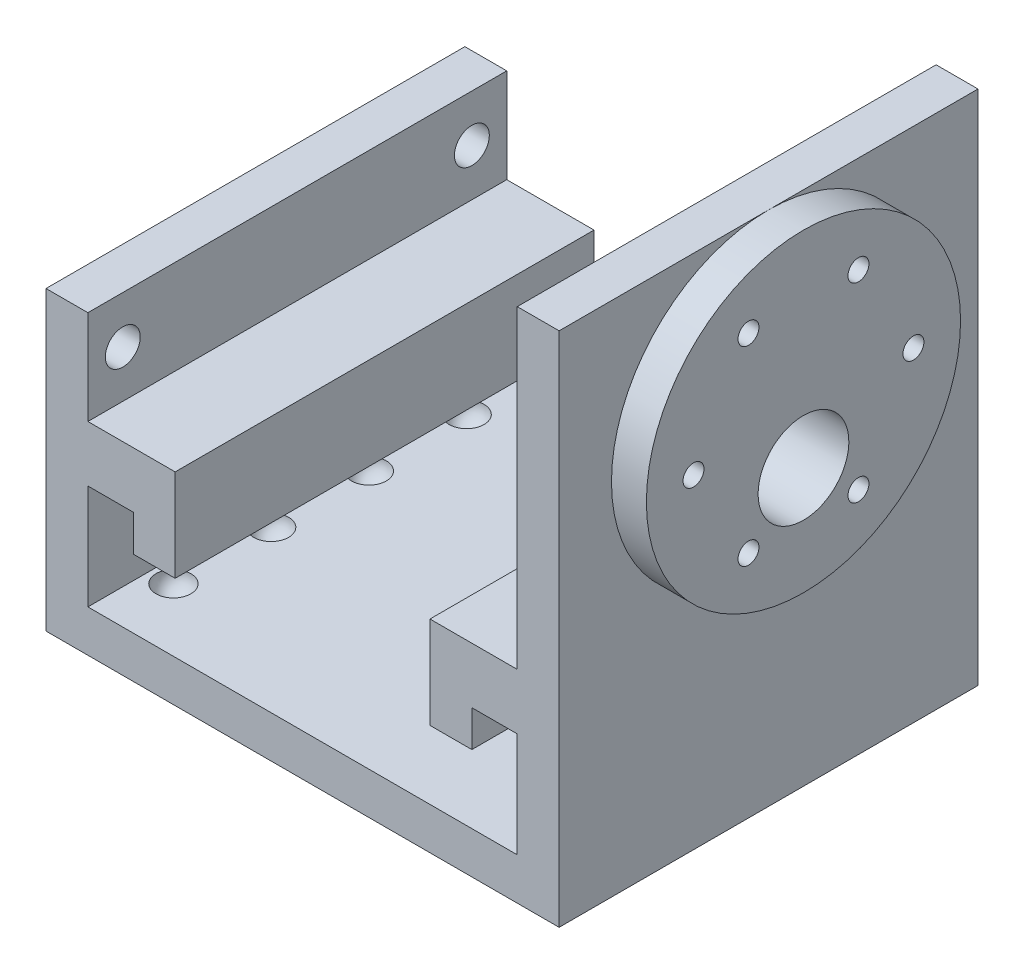
SolidWorks part; units mm, degrees
material "Nylon 101"
ref_plane "Front Plane" through (0, 0, 0) normal (0, 0, 1) x (1, 0, 0)
ref_plane "Top Plane" through (0, 0, 0) normal (0, 1, 0) x (1, 0, 0)
ref_plane "Right Plane" through (0, 0, 0) normal (1, 0, 0) x (0, 0, -1)
sketch "Sketch1" plane through (0, 0, 0) normal (0, 0, 1) x (1, 0, 0)
  line L0 (0, 29) -> (0, 0)
  line L1 (0, 0) -> (73.5, 0)
  line L2 (73.5, 0) -> (73.5, 74)
  line L3 (73.5, 74) -> (67.5, 74)
  line L4 (67.5, 74) -> (67.5, 29)
  line L5 (67.5, 6) -> (6, 6)
  line L6 (6, 6) -> (6, 21)
  line L7 (6, 21) -> (12.5, 21)
  line L8 (0, 29) -> (18.5, 29)
  line L10 (12.5, 21) -> (12.5, 15.8)
  line L11 (12.5, 15.8) -> (18.5, 15.8)
  line L12 (18.5, 15.8) -> (18.5, 29)
  line L13 (67.5, 29) -> (55, 29)
  line L14 (55, 29) -> (55, 15.8)
  line L15 (55, 15.8) -> (61, 15.8)
  line L16 (61, 15.8) -> (61, 21)
  line L17 (61, 21) -> (67.5, 21)
  line L18 (67.5, 21) -> (67.5, 6)
  dimension "D1" = 8
  dimension "D2" = 6
  dimension "D3" = 6
  dimension "D4" = 5.2
  dimension "D5" = 15
  dimension "D6" = 6
  dimension "D7" = 6.5
  dimension "D8" = 6.5
  dimension "D9" = 6
  dimension "D10" = 61.5
  dimension "D11" = 6
  dimension "D12" = 45
extrude "Boss-Extrude1" add sketch "Sketch1" along normal blind 60
sketch "Sketch2" plane through (67.5, 0, 0) normal (-1, 0, 0) x (0, 0, 1)
  circle A0 centre (30, 51.5) radius 15.75 construction
  circle A1 centre (45.75, 51.5) radius 1.5
  dimension "D3" = 31.5
  dimension "D2" = 51.5
  dimension "D4" = 3
  dimension "D1" = 30
extrude "Cut-Extrude1" cut sketch "Sketch2" against normal blind 6
sketch "Sketch3" plane through (0, 21, 0) normal (0, -1, 0) x (1, 0, 0)
  line L0 (61.75, 51) -> (66.75, 51)
  line L2 (0, 60) -> (73.5, 60) construction
  line L4 (61, 60) -> (61, 0) construction
  arc A0 (66.75, 51) -> (61.75, 51) centre (64.25, 51) ccw
  dimension "D1" = 5
  dimension "D2" = 9
  dimension "D3" = 3.25
revolve "Cut-Revolve1" cut sketch "Sketch3" angle 360 about L0
pattern_linear "LPattern1" count 4 spacing 14 along (0, 0, -1) count 2 spacing 55 along (-1, 0, 0) of "Cut-Revolve1"
ref_plane "Plane1" through (36.75, 0, 0) normal (-1, 0, 0) x (0, 0, 1)
ref_axis "Axis1" through (67.5, 51.5, 30) along (-1, 0, 0)
pattern_circular "CirPattern2" count 6 over 360 about axis through (67.5, 51.5, 30) along (-1, 0, 0) of "Cut-Extrude1"
sketch "Sketch10" plane through (67.5, 0, 0) normal (-1, 0, 0) x (0, 0, 1)
  circle A0 centre (30, 44.5) radius 6.5
  dimension "D1" = 13
  dimension "D2" = 7
extrude "Cut-Extrude4" cut sketch "Sketch10" against normal blind 10
sketch "Sketch11" plane through (73.5, 0, 0) normal (1, 0, 0) x (0, 0, -1)
  line L0 (-60, 74) -> (0, 74) construction
  circle A0 centre (-30, 51.5) radius 22.5
  circle A1 centre (-37.875, 65.1399) radius 1.5 construction
  circle A2 centre (-22.125, 65.1399) radius 1.5 construction
  circle A3 centre (-14.25, 51.5) radius 1.5 construction
  circle A4 centre (-22.125, 37.8601) radius 1.5 construction
  circle A5 centre (-30, 44.5) radius 6.5 construction
  circle A6 centre (-37.875, 37.8601) radius 1.5 construction
  circle A7 centre (-45.75, 51.5) radius 1.5 construction
  circle A8 centre (-37.875, 65.1399) radius 1.5
  circle A9 centre (-22.125, 65.1399) radius 1.5
  circle A10 centre (-14.25, 51.5) radius 1.5
  circle A11 centre (-22.125, 37.8601) radius 1.5
  circle A12 centre (-30, 44.5) radius 6.5
  circle A13 centre (-37.875, 37.8601) radius 1.5
  circle A14 centre (-45.75, 51.5) radius 1.5
extrude "Boss-Extrude6" add sketch "Sketch11" along normal blind 5
sketch "Sketch12" plane through (0, 0, 70) normal (1, 0, 0) x (0, 0, -1)
  line L1 (70, 29) -> (70, 0) construction
  line L2 (10, 29) -> (70, 29)
  line L3 (10, 29) -> (10, 42.5)
  line L4 (10, 42.5) -> (70, 42.5)
  line L5 (70, 29) -> (70, 42.5)
  circle A0 centre (15, 35.75) radius 2.5
  circle A1 centre (65, 35.75) radius 2.5
  dimension "D5" = 5
  dimension "D1" = 13.5
  dimension "D2" = 50
  dimension "D3" = 6.75
  dimension "D4" = 5
extrude "Boss-Extrude7" add sketch "Sketch12" along normal up to surface (6 mm away) up to face at (6, 13.5, 30)
ref_plane "Plane2" through (0, 13.5, 0) normal (0, 1, 0) x (1, 0, 0)
mirror "Mirror1" about plane through (0, 13.5, 0) normal (0, 1, 0) of "Cut-Revolve1", "LPattern1"
